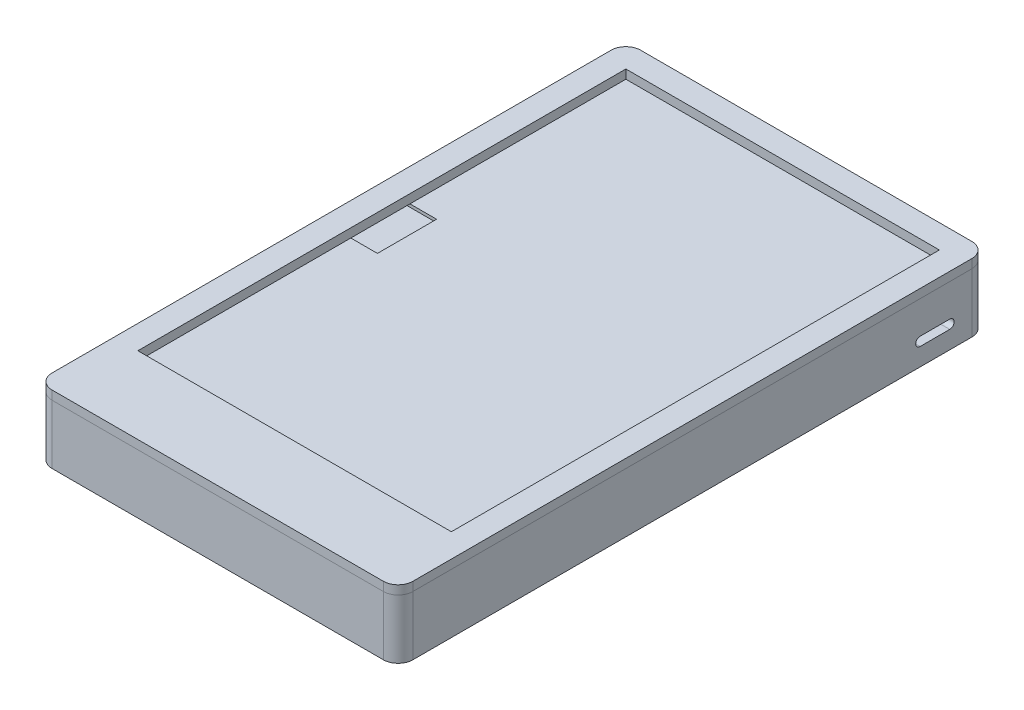
SolidWorks part; units mm, degrees
ref_plane "Front Plane" through (0, 0, 0) normal (0, 0, 1) x (1, 0, 0)
ref_plane "Top Plane" through (0, 0, 0) normal (0, 1, 0) x (1, 0, 0)
ref_plane "Right Plane" through (0, 0, 0) normal (1, 0, 0) x (0, 0, -1)
sketch "Sketch2" plane through (0, 0, 0) normal (0, 1, 0) x (1, 0, 0)
  line L1 (-56, -85.5) -> (56, -85.5)
  line L2 (-56, -85.5) -> (-56, 85.5)
  line L3 (-56, 85.5) -> (56, 85.5)
  line L4 (56, -85.5) -> (56, 85.5)
  line L5 (-56, -85.5) -> (56, 85.5) construction
  line L6 (-56, 85.5) -> (56, -85.5) construction
  point P0 (0, 0)
  dimension "D1" = 112
  dimension "D2" = 171
extrude "Boss-Extrude1" add sketch "Sketch2" along normal blind 2
sketch "Sketch3" plane through (0, 2, 0) normal (0, 1, 0) x (1, 0, 0)
  line L0 (61, -85.5) -> (61, 85.5)
  line L1 (56, 90.5) -> (-56, 90.5)
  line L2 (-61, 85.5) -> (-61, -85.5)
  line L4 (56, -85.5) -> (56, 85.5)
  line L5 (56, 85.5) -> (-56, 85.5)
  line L6 (-56, 85.5) -> (-56, -85.5)
  line L7 (-56, -85.5) -> (56, -85.5)
  line L8 (56, -85.5) -> (56, 85.5)
  line L9 (56, 85.5) -> (-56, 85.5)
  line L10 (-56, 85.5) -> (-56, -85.5)
  line L11 (-56, -85.5) -> (56, -85.5)
  line L12 (-61, 90.5) -> (-61, -90.5) construction
  line L13 (-61, -90.5) -> (61, -90.5) construction
  line L14 (61, -90.5) -> (61, 90.5) construction
  line L15 (61, 90.5) -> (-61, 90.5) construction
  line L16 (-61, -85.5) -> (-61, -103.5)
  line L17 (-56, -108.5) -> (56, -108.5)
  line L18 (61, -103.5) -> (61, -85.5)
  arc A2 (56, 90.5) -> (61, 85.5) centre (56, 85.5) cw
  arc A3 (-61, 85.5) -> (-56, 90.5) centre (-56, 85.5) cw
  arc A4 (61, -103.5) -> (56, -108.5) centre (56, -103.5) cw
  arc A5 (-61, -103.5) -> (-56, -108.5) centre (-56, -103.5) ccw
  point P23 (-61, -108.5)
  dimension "D3" = 23
  dimension "D4" = 5
  dimension "D5" = 5
  dimension "D1" = 0
  dimension "D2" = 5
extrude "Boss-Extrude2" add sketch "Sketch3" against normal blind 20 separate body
sketch "Sketch4" plane through (0, -18, 0) normal (0, -1, 0) x (1, 0, 0)
  line L0 (56, -90.5) -> (-56, -90.5) construction
  line L1 (61, 103.5) -> (61, -85.5) construction
  line L3 (-61, -85.5) -> (-61, 103.5) construction
  line L4 (56, -90.5) -> (-56, -90.5)
  line L5 (61, 103.5) -> (61, -85.5)
  line L7 (-61, -85.5) -> (-61, 103.5)
  line L8 (-56, 108.5) -> (56, 108.5) construction
  line L9 (-56, 108.5) -> (56, 108.5)
  arc A0 (-61, -85.5) -> (-56, -90.5) centre (-56, -85.5) ccw construction
  arc A1 (56, -90.5) -> (61, -85.5) centre (56, -85.5) ccw construction
  arc A4 (-61, -85.5) -> (-56, -90.5) centre (-56, -85.5) ccw
  arc A5 (56, -90.5) -> (61, -85.5) centre (56, -85.5) ccw
  arc A8 (-56, 108.5) -> (-61, 103.5) centre (-56, 103.5) ccw construction
  arc A9 (-56, 108.5) -> (-61, 103.5) centre (-56, 103.5) ccw
  arc A10 (61, 103.5) -> (56, 108.5) centre (56, 103.5) ccw construction
  arc A11 (61, 103.5) -> (56, 108.5) centre (56, 103.5) ccw
extrude "Boss-Extrude3" add sketch "Sketch4" along normal blind 3
sketch "Sketch6" plane through (0, -18, 0) normal (0, 1, 0) x (1, 0, 0)
  line L1 (-3.3, 60.5) -> (56, 60.5)
  line L2 (-3.3, 60.5) -> (-3.3, 85.5)
  line L3 (-3.3, 85.5) -> (56, 85.5)
  line L4 (56, 60.5) -> (56, 85.5)
  line L5 (-3.3, 60.5) -> (56, 85.5) construction
  line L6 (-3.3, 85.5) -> (56, 60.5) construction
  point P0 (26.35, 73)
  dimension "D1" = 25
  dimension "D2" = 59.3
extrude "Boss-Extrude4" add sketch "Sketch6" along normal blind 2 separate body
sketch "Sketch7" plane through (0, 0, 85.5) normal (0, 0, -1) x (-1, 0, 0)
  line L0 (-56, -18) -> (-56, 2) construction
  line L1 (-56, 0) -> (56, 0)
  line L2 (-56, 0) -> (-56, -18)
  line L3 (-56, -18) -> (56, -18)
  line L4 (56, 0) -> (56, -18)
  line L5 (56, 2) -> (-56, 2) construction
  dimension "D1" = 2
extrude "Cut-Extrude1" cut sketch "Sketch7" against normal offset from surface (21 mm away) 2 up to face at (0, -9.5, 108.5)
sketch "Sketch8" plane through (0, -18, 0) normal (0, 1, 0) x (1, 0, 0)
  line L0 (56, -106.5) -> (56, 85.5) construction
  line L1 (-4, 55.5) -> (56, 55.5)
  line L2 (-4, 55.5) -> (-4, -42.5)
  line L3 (-4, -42.5) -> (56, -42.5)
  line L4 (56, 55.5) -> (56, -42.5)
  line L5 (-3.3, 60.5) -> (56, 60.5) construction
  dimension "D1" = 5
  dimension "D2" = 60
  dimension "D3" = 98
extrude "Boss-Extrude5" add sketch "Sketch8" along normal blind 9 separate body
sketch "Sketch9" plane through (0, -18, 0) normal (0, 1, 0) x (1, 0, 0)
  line L0 (-56, 85.5) -> (-56, -106.5) construction
  line L1 (-56, 65.5) -> (-26, 65.5)
  line L2 (-56, 65.5) -> (-56, 0.5)
  line L3 (-56, 0.5) -> (-26, 0.5)
  line L4 (-26, 65.5) -> (-26, 0.5)
  line L5 (56, 85.5) -> (-56, 85.5) construction
  line L6 (-56, 85.5) -> (-56, -85.5) construction
  line L7 (-56, -4.5) -> (-25, -4.5)
  line L8 (-56, -4.5) -> (-56, -69.8)
  line L9 (-56, -69.8) -> (-25, -69.8)
  line L10 (-25, -4.5) -> (-25, -69.8)
  dimension "D1" = 30
  dimension "D2" = 65
  dimension "D3" = 20
  dimension "D4" = 31
  dimension "D5" = 65.3
  dimension "D6" = 5
extrude "Boss-Extrude6" add sketch "Sketch9" along normal blind 7 separate body
sketch "Sketch10" plane through (0, -18, 0) normal (0, 1, 0) x (1, 0, 0)
  line L0 (-10.5, -32.65) -> (-4.8608, -32.65)
  line L1 (-43, -6) -> (-43, -32.65)
  line L2 (-43, -74.3) -> (-10.5, -74.3)
  line L3 (-56, -6) -> (-46, -6)
  line L4 (-10.5, -74.3) -> (-10.5, -47.65)
  line L5 (-56, -1) -> (-24.5, -1)
  line L7 (-21.5, -1) -> (-7.8, -1)
  line L8 (-56, 85.5) -> (-56, -85.5) construction
  line L9 (-56, 85.5) -> (-56, -106.5) construction
  line L13 (-24.5, -1) -> (-24.5, 67)
  line L14 (-24.5, 67) -> (-56, 67)
  line L15 (-7.8608, -47) -> (-7.8608, 60) construction
  line L16 (-7.8, -1) -> (-7.8, 85.5)
  line L17 (-56, 0.5) -> (-26, 0.5) construction
  line L18 (-26, 0.5) -> (-26, 65.5) construction
  line L19 (-26, 65.5) -> (-56, 65.5) construction
  line L23 (-4.8608, -77.3) -> (-46, -77.3)
  line L24 (-21.5, -1) -> (-21.5, 70)
  line L25 (-21.5, 70) -> (-56, 70)
  line L26 (-56, -4) -> (-21.5, -4) construction
  line L27 (-21.5, -4) -> (-21.5, 70) construction
  line L28 (-4.8, 85.5) -> (-4.8, 59)
  line L29 (56, 85.5) -> (-56, 85.5) construction
  line L30 (-4.8, 59) -> (56, 59)
  line L31 (56, -106.5) -> (56, 85.5) construction
  line L32 (-3.3, 85.5) -> (-3.3, 60.5) construction
  line L33 (-3.3, 60.5) -> (56, 60.5) construction
  line L34 (56, -44) -> (15.1392, -44)
  line L35 (56, -85.5) -> (56, 85.5) construction
  line L36 (-4.8608, -32.65) -> (-4.8608, 57)
  line L37 (-7.8, 85.5) -> (-4.8, 85.5)
  line L39 (-4.8608, 57) -> (56, 57)
  line L40 (56, 55.5) -> (-4, 55.5) construction
  line L42 (56, -47) -> (15.1392, -47)
  line L43 (-4.8608, -77.3) -> (-4.8608, -47.65)
  line L46 (-7.8608, 60) -> (56, 60) construction
  line L47 (56, -47) -> (-7.8608, -47) construction
  line L48 (56, -44) -> (56, -47)
  line L49 (56, 59) -> (56, 57)
  line L51 (-56, 67) -> (-56, 70)
  line L52 (-56, -6) -> (-56, -1)
  line L54 (-46, -77.3) -> (-46, -47.65)
  line L55 (-43, -6) -> (-10.5, -6)
  line L56 (-46, -47.65) -> (-43, -47.65)
  line L57 (-46, -32.65) -> (-43, -32.65)
  line L58 (-43, -47.65) -> (-43, -74.3)
  line L59 (-46, -32.65) -> (-46, -6)
  line L60 (-10.5, -47.65) -> (-4.8608, -47.65)
  line L61 (-10.5, -32.65) -> (-10.5, -6)
  line L62 (-4.8608, -44) -> (-4.8608, 57) construction
  line L63 (15.1392, -44) -> (15.1392, -47)
  line L64 (56, -44) -> (-4.8608, -44) construction
  point P63 (0, 0)
  point P64 (0, 0)
  point P65 (0, 0)
  point P66 (0, 0)
  dimension "D2" = 3
  dimension "D3" = 5
  dimension "D4" = 1.5
  dimension "D5" = 1.5
  dimension "D6" = 1.5
  dimension "D7" = 3
  dimension "D9" = 1.5
  dimension "D10" = 1.5
  dimension "D11" = 3
  dimension "D12" = 15
  dimension "D13" = 1.5
  dimension "D16" = 101
  dimension "D17" = 20
  dimension "D18" = 10
  dimension "D19" = 32.5
  dimension "D20" = 68.3
  dimension "D14" = 60.8608
  dimension "D15" = 3
  dimension "D8" = 3
extrude "Boss-Extrude7" add sketch "Sketch10" along normal blind 3 separate body
combine bodies "Combine1" operation type add bodies to combine 109 105
combine bodies "Combine2" operation type add bodies to combine 111 155 156
sketch "Sketch11" plane through (-56, 0, 0) normal (1, 0, 0) x (0, 0, -1)
  line L0 (85.5, -18) -> (85.5, 2) construction
  line L1 (69.5, -5) -> (80.5, -5)
  line L2 (69.5, -5) -> (69.5, -11)
  line L3 (69.5, -11) -> (80.5, -11)
  line L4 (80.5, -5) -> (80.5, -11)
  point P8 (85.5, -8)
  point P9 (80.5, -8)
  dimension "D1" = 11
  dimension "D2" = 6
  dimension "D3" = 5
extrude "Cut-Extrude2" cut sketch "Sketch11" against normal blind 13
sketch "Sketch13" plane through (0, -18, 0) normal (0, 1, 0) x (1, 0, 0)
  line L0 (-56, -6) -> (-56, -106.5) construction
  line L1 (-56, -82.5) -> (56, -82.5)
  line L2 (-56, -82.5) -> (-56, -85.5)
  line L3 (-56, -85.5) -> (56, -85.5)
  line L4 (56, -82.5) -> (56, -85.5)
  dimension "D1" = 3
extrude "Boss-Extrude8" add sketch "Sketch13" along normal blind 13 separate body
combine bodies "Combine3" operation type add bodies to combine 114 113
sketch "Sketch15" plane through (0, -5, 0) normal (0, 1, 0) x (1, 0, 0)
  line L0 (-56, -82.5) -> (-56, -74.5)
  line L5 (-56, -74.5) -> (-53, -74.5)
  line L6 (-53, -74.5) -> (-53, -79.5)
  line L7 (-53, -79.5) -> (-48, -79.5)
  line L8 (-48, -79.5) -> (-48, -82.5)
  line L9 (56, -82.5) -> (-56, -82.5) construction
  line L10 (-48, -82.5) -> (-56, -82.5)
  dimension "D1" = 8
  dimension "D2" = 8
  dimension "D3" = 3
  dimension "D4" = 3
extrude "Boss-Extrude10" add sketch "Sketch15" against normal blind 3 separate body
mirror "Mirror2" about plane through (0, 0, 0) normal (1, 0, 0) of "Boss-Extrude10"
combine bodies "Combine7" operation type add bodies to combine 117 118
ref_plane "Plane1" through (0, 0, -1.5) normal (0, 0, 1) x (1, 0, 0)
sketch "Sketch16" plane through (0, -18, 0) normal (0, 1, 0) x (1, 0, 0)
  line L1 (-56, 85.5) -> (-48, 85.5)
  line L2 (-56, 85.5) -> (-56, 77.5)
  line L3 (-56, 77.5) -> (-53, 77.5)
  line L4 (-48, 85.5) -> (-48, 82.5)
  line L7 (-48, 82.5) -> (-53, 82.5)
  line L8 (-53, 77.5) -> (-53, 82.5)
  dimension "D1" = 3
  dimension "D2" = 3
  dimension "D3" = 5
  dimension "D4" = 5
extrude "Boss-Extrude11" add sketch "Sketch16" along normal blind 3 from offset 10 separate body
mirror "Mirror4" about plane through (0, 0, 0) normal (1, 0, 0) of "Boss-Extrude11"
sketch "Sketch17" plane through (0, 0, -85.5) normal (0, 0, 1) x (1, 0, 0)
  line L0 (-48, -5) -> (-48, -8) construction
  line L1 (-40, -6) -> (-29, -6)
  line L2 (-40, -6) -> (-40, -12)
  line L3 (-40, -12) -> (-29, -12)
  line L4 (-29, -6) -> (-29, -12)
  line L5 (-7.8, -18) -> (-56, -18) construction
  dimension "D1" = 11
  dimension "D2" = 6
  dimension "D3" = 8
  dimension "D4" = 6
extrude "Cut-Extrude3" cut sketch "Sketch17" against normal blind 13
sketch "Sketch18" plane through (0, -11, 0) normal (0, 1, 0) x (1, 0, 0)
  line L4 (-61, 80.5) -> (-61, 69.5)
  line L5 (-61, 69.5) -> (-56, 69.5)
  line L6 (-56, 69.5) -> (-56, 80.5)
  line L7 (-56, 80.5) -> (-61, 80.5)
  line L8 (-61, 80.5) -> (-61, 69.5)
  line L9 (-61, 69.5) -> (-56, 69.5)
  line L10 (-56, 69.5) -> (-56, 80.5)
  line L11 (-56, 80.5) -> (-61, 80.5)
  dimension "D1" = 0
extrude "Boss-Extrude12" add sketch "Sketch18" along normal up to surface (6 mm away) up to face at (-58.5, -5, -75)
sketch "Sketch19" plane through (0, -5, 0) normal (0, 1, 0) x (1, 0, 0)
  line L0 (-56, -74.5) -> (-56, -85.5) construction
  line L1 (-56, -82.5) -> (56, -82.5)
  line L2 (-56, -82.5) -> (-56, -85.5)
  line L3 (-56, -85.5) -> (56, -85.5)
  line L4 (56, -82.5) -> (56, -85.5)
  line L5 (56, -82.5) -> (-56, -82.5) construction
extrude "Boss-Extrude13" add sketch "Sketch19" along normal blind 2
sketch "Sketch20" plane through (0, -5, 0) normal (0, 1, 0) x (1, 0, 0)
  line L1 (-56, 85.5) -> (56, 85.5)
  line L2 (-56, 85.5) -> (-56, -82.5)
  line L3 (-56, -82.5) -> (56, -82.5)
  line L4 (56, 85.5) -> (56, -82.5)
extrude "Boss-Extrude14" add sketch "Sketch20" against normal blind 1 from surface at 2 separate body starting at face at (0, -3, 84)
sketch "Sketch21" plane through (0, -4, 0) normal (0, -1, 0) x (-1, 0, 0)
  line L1 (56, -8.5) -> (46, -8.5)
  line L2 (56, -8.5) -> (56, 11.5)
  line L3 (56, 11.5) -> (46, 11.5)
  line L4 (46, -8.5) -> (46, 11.5)
  line L5 (56, -8.5) -> (46, 11.5) construction
  line L6 (56, 11.5) -> (46, -8.5) construction
  line L8 (56, 85.5) -> (56, -82.5) construction
  point P5 (56, 1.5)
  point P6 (56, 1.5)
  point P7 (0, 0)
  dimension "D1" = 20
  dimension "D2" = 10
extrude "Cut-Extrude4" cut sketch "Sketch21" against normal blind 1
sketch "Sketch22" plane through (0, 2, 0) normal (0, 1, 0) x (1, 0, 0)
  line L0 (56, -85.5) -> (56, 85.5) construction
  line L1 (56, 85.5) -> (-56, 85.5) construction
  line L2 (-56, 85.5) -> (-56, -85.5) construction
  line L3 (-56, -85.5) -> (56, -85.5) construction
  line L4 (56, -85.5) -> (56, 85.5)
  line L5 (56, 85.5) -> (-56, 85.5)
  line L6 (-56, 85.5) -> (-56, -85.5)
  line L7 (-56, -85.5) -> (56, -85.5)
  line L8 (-53, 82.5) -> (-53, -82.5)
  line L9 (-53, -82.5) -> (53, -82.5)
  line L10 (53, -82.5) -> (53, 82.5)
  line L11 (53, 82.5) -> (-53, 82.5)
  dimension "D1" = 3
extrude "Boss-Extrude15" add sketch "Sketch22" against normal blind 3
ref_plane "Plane2" through (0, -1, 0) normal (0, -1, 0) x (-1, 0, 0)
split "Split1" trim tools "Plane2" bodies to split 127 resulting bodies 128 129
sketch "Sketch23" plane through (0, -18, 0) normal (0, 1, 0) x (1, 0, 0)
  line L0 (56, -106.5) -> (56, 85.5) construction
  line L1 (-56, -85.5) -> (56, -85.5)
  line L2 (-56, -85.5) -> (-56, -88.5)
  line L3 (-56, -88.5) -> (56, -88.5)
  line L4 (56, -85.5) -> (56, -88.5)
  dimension "D1" = 3
extrude "Boss-Extrude16" add sketch "Sketch23" along normal up to surface (17 mm away)
delete or keep bodies "Body-Delete/Keep 1" type delete bodies bodies 101
sketch "Sketch24" plane through (0, -4, 0) normal (0, -1, 0) x (-1, 0, 0)
  line L1 (56, 85.5) -> (-56, 85.5)
  line L2 (56, 85.5) -> (56, -85.5)
  line L3 (56, -85.5) -> (-56, -85.5)
  line L4 (-56, 85.5) -> (-56, -85.5)
extrude "Boss-Extrude17" add sketch "Sketch24" along normal blind 2 separate body
sketch "Sketch25" plane through (0, 0, 88.5) normal (0, 0, 1) x (1, 0, 0)
  line L0 (-56, -18) -> (56, -18) construction
  line L1 (-46, -18) -> (46, -18)
  line L2 (-46, -18) -> (-46, -10)
  line L3 (-46, -10) -> (46, -10)
  line L4 (46, -18) -> (46, -10)
  line L5 (-56, -1) -> (-56, -18) construction
  line L6 (56, -1) -> (56, -18) construction
  dimension "D1" = 10
  dimension "D2" = 10
  dimension "D3" = 8
extrude "Cut-Extrude5" cut sketch "Sketch25" against normal blind 6
sketch "Sketch26" plane through (0, 0, 0) normal (0, -1, 0) x (-1, 0, 0)
  line L0 (0, -85.5) -> (0, -108.5) construction
  line L1 (15.5, -89) -> (-15.5, -89)
  line L2 (15.5, -89) -> (15.5, -106)
  line L3 (15.5, -106) -> (-15.5, -106)
  line L4 (-15.5, -89) -> (-15.5, -106)
  line L5 (15.5, -89) -> (-15.5, -106) construction
  line L6 (15.5, -106) -> (-15.5, -89) construction
  line L7 (56, -85.5) -> (-56, -85.5) construction
  line L8 (56, -108.5) -> (-56, -108.5) construction
  line L9 (56, -106.5) -> (-56, -106.5) construction
  line L10 (-50.1, -89) -> (-50.1, -106)
  line L11 (-19.1, -106) -> (-50.1, -106)
  line L12 (-19.1, -89) -> (-19.1, -106)
  line L13 (-19.1, -89) -> (-50.1, -89)
  line L14 (19.9, -89) -> (19.9, -106)
  line L15 (50.9, -106) -> (19.9, -106)
  line L16 (50.9, -89) -> (50.9, -106)
  line L17 (50.9, -89) -> (19.9, -89)
  line L18 (56, -106.5) -> (56, -85.5) construction
  line L20 (-56, -106.5) -> (-56, -85.5) construction
  line L21 (56, -85.5) -> (-56, -85.5) construction
  line L22 (-56, -106.5) -> (-56, -85.5)
  line L23 (56, -106.5) -> (-56, -106.5)
  line L24 (56, -106.5) -> (56, -85.5)
  line L25 (56, -85.5) -> (-56, -85.5)
  point P0 (0, -97.5)
  dimension "D1" = 17
  dimension "D2" = 31
  dimension "D3" = 0.5
  dimension "D6" = 5.1
  dimension "D7" = 75.1
  dimension "D4" = 2
  dimension "D5" = 2
extrude "Boss-Extrude18" add sketch "Sketch26" along normal blind 1
sketch "Sketch27" plane through (0, -15, 0) normal (0, 1, 0) x (1, 0, 0)
  line L0 (-21.5, 70) -> (-56, 70) construction
  line L1 (-48, 70) -> (-28.5, 70)
  line L2 (-48, 70) -> (-48, 67)
  line L3 (-48, 67) -> (-28.5, 67)
  line L4 (-28.5, 70) -> (-28.5, 67)
  line L5 (-56, 67) -> (-24.5, 67) construction
  line L6 (-56, 85.5) -> (-56, -85.5) construction
  dimension "D1" = 8
  dimension "D2" = 4
extrude "Cut-Extrude6" cut sketch "Sketch27" against normal up to surface (3 mm away) up to face at (25.6, -18, -72.25)
sketch "Sketch28" plane through (-56, 0, 0) normal (1, 0, 0) x (0, 0, -1)
  line L0 (67, -18) -> (-1, -18) construction
  line L1 (-82.5, -8) -> (-82.5, -18) construction
  line L2 (-6, -18) -> (-82.5, -18) construction
  ellipse E0 centre (10.9166, -15.2) end of major axis (5.6054, -15.2) minor radius 2.7092
  dimension "D1" = 2.8
  dimension "D2" = 88.1054
  dimension "D3" = 93.4166
  dimension "D4" = 0.0908
extrude "Cut-Extrude7" cut sketch "Sketch28" against normal blind 10
sketch "Sketch29" plane through (-56, 0, 0) normal (1, 0, 0) x (0, 0, -1)
  line L0 (10.9166, -15.2) -> (85.5, -15.2) construction
  line L1 (85.5, -18) -> (85.5, -8) construction
  line L2 (46.1027, -18) -> (58.3512, -18)
  line L3 (67, -18) -> (-1, -18) construction
  line L4 (-82.5, -8) -> (-82.5, -18) construction
  line L5 (-6, -18) -> (-82.5, -18) construction
  ellipse E0 centre (10.9166, -15.2) end of major axis (5.6054, -15.2) minor radius 2.7092 construction
  ellipse E1 centre (23.4365, -15.2) end of major axis (18.1254, -15.2) minor radius 2.7092
  ellipse E2 centre (52.702, -15.2) end of major axis (44.4022, -15.6719) minor radius 4.1446 (58.3512, -18) -> (46.1027, -18) ccw
  dimension "D1" = 100.6254
  dimension "D2" = 105.9365
  dimension "D3" = 126.9022
  dimension "D4" = 128.6027
  dimension "D5" = 134.9668
  dimension "D6" = 135.202
  dimension "D7" = 0.0908
extrude "Cut-Extrude8" cut sketch "Sketch29" against normal blind 2
sketch "Sketch30" plane through (-58, 0, 0) normal (1, 0, 0) x (0, 0, -1)
  ellipse E1 centre (23.4365, -15.2) end of major axis (18.1254, -15.2) minor radius 2.7092
  ellipse E2 centre (23.4365, -15.2) end of major axis (18.1254, -15.2) minor radius 2.7092
  dimension "D1" = 0
extrude "Cut-Extrude9" cut sketch "Sketch30" against normal blind 11.5
sketch "Sketch31" plane through (-61, 0, 0) normal (-1, 0, 0) x (0, 0, 1)
  ellipse E0 centre (-10.9166, -15.2) end of major axis (-5.6054, -15.2) minor radius 2.7092 construction
  ellipse E1 centre (-10.9166, -15.2) end of major axis (-5.6054, -15.2) minor radius 2.7092
extrude "Boss-Extrude19" add sketch "Sketch31" against normal blind 3
sketch "Sketch32" plane through (0, 0, -85.5) normal (0, 0, 1) x (1, 0, 0)
  line L1 (-3.3, -11) -> (56, -11)
  line L6 (-3.3, -18) -> (-3.3, -11)
  line L7 (-3.3, -18) -> (56, -18)
  line L8 (56, -18) -> (56, -8) construction
  line L9 (56, -18) -> (56, -11)
  dimension "D1" = 7
extrude "Cut-Extrude10" cut sketch "Sketch32" against normal blind 3.5
sketch "Sketch33" plane through (0, 0, -89) normal (0, 0, 1) x (1, 0, 0)
  line L2 (-4.8, -16) -> (8.2, -16)
  line L3 (-4.8, -16) -> (-4.8, -12)
  line L4 (-4.8, -12) -> (8.2, -12)
  line L5 (8.2, -16) -> (8.2, -12)
  line L6 (-4.8, -16) -> (8.2, -12) construction
  line L7 (-4.8, -12) -> (8.2, -16) construction
  line L8 (-3.3, -11) -> (-3.3, -18) construction
  line L9 (-3.3, -18) -> (56, -18) construction
  dimension "D1" = 13
  dimension "D2" = 4
  dimension "D3" = 1.5
  dimension "D4" = 2
extrude "Cut-Extrude11" cut sketch "Sketch33" against normal blind 3
sketch "Sketch35" plane through (56, 0, 0) normal (-1, 0, 0) x (0, 0, 1)
  line L0 (-78, -13.5) -> (-68, -13.5) construction
  line L1 (-78, -12) -> (-68, -12)
  line L2 (-78, -15) -> (-68, -15)
  line L3 (-60.5, -16) -> (-85.5, -16) construction
  line L4 (-73, -16) -> (-73, -12) construction
  arc A0 (-78, -12) -> (-78, -15) centre (-78, -13.5) ccw
  arc A1 (-68, -15) -> (-68, -12) centre (-68, -13.5) ccw
  point P2 (-73, -13.5)
  dimension "D1" = 10
  dimension "D2" = 3
  dimension "D3" = 1
extrude "Cut-Extrude13" cut sketch "Sketch35" against normal blind 22
chamfer "Chamfer1" distance 3 angle 45 8 edges at (56, -8, 78.5) (52, -8, 82.5) (-56, -8, 78.5) (-52, -8, 82.5) (-52, -8, -85.5) (-56, -8, -81.5) (56, -8, -81.5) (52, -8, -85.5)
sketch "Sketch37" plane through (0, 0, -89) normal (0, 0, -1) x (-1, 0, 0)
  line L4 (3.3, -12) -> (3.3, -16)
  line L5 (3.3, -16) -> (4.8, -16)
  line L6 (4.8, -16) -> (4.8, -12)
  line L7 (4.8, -12) -> (3.3, -12)
  line L8 (3.3, -12) -> (3.3, -16)
  line L9 (3.3, -16) -> (4.8, -16)
  line L10 (4.8, -16) -> (4.8, -12)
  line L11 (4.8, -12) -> (3.3, -12)
  dimension "D1" = 0
extrude "Cut-Extrude14" cut sketch "Sketch37" against normal blind 10
sketch "Sketch38" plane through (0, 0, -85.5) normal (0, 0, 1) x (1, 0, 0)
  line L4 (-3.3, -18) -> (-3.3, -16)
  line L5 (-3.3, -16) -> (-4.8, -16)
  line L6 (-4.8, -16) -> (-4.8, -18)
  line L7 (-4.8, -18) -> (-3.3, -18)
  line L8 (-3.3, -18) -> (-3.3, -16)
  line L9 (-3.3, -16) -> (-4.8, -16)
  line L10 (-4.8, -16) -> (-4.8, -18)
  line L11 (-4.8, -18) -> (-3.3, -18)
  dimension "D1" = 0
extrude "Cut-Extrude15" cut sketch "Sketch38" against normal up to surface (3.5 mm away) up to face at (14.4, -14.25, -89)
sketch "Sketch39" plane through (-3.3, 0, 0) normal (1, 0, 0) x (0, 0, -1)
  line L4 (85.5, -11) -> (85.5, -12)
  line L5 (85.5, -12) -> (89, -12)
  line L6 (89, -12) -> (89, -11)
  line L7 (89, -11) -> (85.5, -11)
  line L8 (85.5, -11) -> (85.5, -12)
  line L9 (85.5, -12) -> (89, -12)
  line L10 (89, -12) -> (89, -11)
  line L11 (89, -11) -> (85.5, -11)
  dimension "D1" = 0
extrude "Cut-Extrude16" cut sketch "Sketch39" against normal up to surface (1.5 mm away) up to face at (-4.8, -15.25, -81)
sketch "Sketch40" plane through (0, -5, 0) normal (0, 1, 0) x (1, 0, 0)
  line L0 (56, 77.5) -> (56, 85.5) construction
  line L1 (56, 85.5) -> (48, 85.5) construction
  line L2 (48, 85.5) -> (48, 82.5) construction
  line L3 (48, 82.5) -> (53, 82.5) construction
  line L4 (53, 82.5) -> (53, 77.5) construction
  line L5 (53, 77.5) -> (56, 77.5) construction
  line L6 (-56, -82.5) -> (-48, -82.5)
  line L7 (-48, -82.5) -> (-48, -79.5)
  line L8 (-48, -79.5) -> (-53, -79.5)
  line L9 (-53, -79.5) -> (-53, -74.5)
  line L10 (-53, -74.5) -> (-56, -74.5)
  line L11 (-56, -74.5) -> (-56, -82.5)
  line L12 (-56, -82.5) -> (-48, -82.5)
  line L13 (-48, -82.5) -> (-48, -79.5)
  line L14 (-48, -79.5) -> (-53, -79.5)
  line L15 (-53, -79.5) -> (-53, -74.5)
  line L16 (-53, -74.5) -> (-56, -74.5)
  line L18 (48, -82.5) -> (56, -82.5)
  line L19 (56, -82.5) -> (56, -74.5)
  line L20 (56, -74.5) -> (53, -74.5)
  line L21 (53, -74.5) -> (53, -79.5)
  line L22 (53, -79.5) -> (48, -79.5)
  line L23 (48, -79.5) -> (48, -82.5)
  line L24 (48, -82.5) -> (56, -82.5)
  line L26 (56, -74.5) -> (53, -74.5)
  line L27 (53, -74.5) -> (53, -79.5)
  line L28 (53, -79.5) -> (48, -79.5)
  line L29 (48, -79.5) -> (48, -82.5)
  line L30 (-56, 85.5) -> (-56, 77.5) construction
  line L31 (-56, 77.5) -> (-53, 77.5) construction
  line L32 (-53, 77.5) -> (-53, 82.5) construction
  line L33 (-53, 82.5) -> (-48, 82.5) construction
  line L34 (-48, 82.5) -> (-48, 85.5) construction
  line L35 (-48, 85.5) -> (-56, 85.5) construction
  line L36 (56, 77.5) -> (56, 85.5)
  line L37 (56, 85.5) -> (48, 85.5)
  line L38 (48, 85.5) -> (48, 82.5)
  line L39 (48, 82.5) -> (53, 82.5)
  line L40 (53, 82.5) -> (53, 77.5)
  line L41 (53, 77.5) -> (56, 77.5)
  line L42 (-56, 85.5) -> (-56, 77.5)
  line L43 (-56, 77.5) -> (-53, 77.5)
  line L44 (-53, 77.5) -> (-53, 82.5)
  line L45 (-53, 82.5) -> (-48, 82.5)
  line L46 (-48, 82.5) -> (-48, 85.5)
  line L47 (-48, 85.5) -> (-56, 85.5)
  line L54 (-56, -74.5) -> (-56, -82.5)
  line L55 (56, -82.5) -> (56, -74.5)
  dimension "D1" = 0
  dimension "D2" = 0
extrude "Boss-Extrude20" add sketch "Sketch40" along normal blind 1
sketch "Sketch41" plane through (0, -1, 0) normal (0, 1, 0) x (1, 0, 0)
  line L0 (-61, -102.5) -> (-56, -102.5) construction
  line L1 (-61, -103.5) -> (-61, 85.5) construction
  line L2 (-56, -88.5) -> (-56, -106.5) construction
  line L3 (-56, -108.5) -> (56, -108.5) construction
  line L4 (-61, 84.5) -> (-56, 84.5) construction
  line L5 (-56, 11.5) -> (-56, 85.5) construction
  line L6 (56, 90.5) -> (-56, 90.5) construction
  line L7 (-56, 0) -> (-61, 0) construction
  line L8 (-56, 85.5) -> (-56, -85.5) construction
  circle A0 centre (-58.5, -102.5) radius 2
  circle A1 centre (-58.5, 84.5) radius 2
  circle A2 centre (-58.5, 0) radius 2
  point P25 (0, 0)
  dimension "D1" = 4
  dimension "D3" = 4
  dimension "D4" = 6
  dimension "D5" = 4
  dimension "D2" = 6
extrude "Boss-Extrude21" add sketch "Sketch41" along normal blind 2
hole_wizard "Ø1.0mm Dowel Hole1" positions "Sketch55" profile "Sketch57" hole size "Ø1.0" standard "ANSI Metric"
sketch "Sketch55" plane through (0, 1, 0) normal (0, 1, 0) x (1, 0, 0)
  point P0 (-58.5, -102.5)
  point P3 (-58.5, 0)
  point P6 (-58.5, 84.5)
sketch "Sketch57" plane through (-58.5, 1, 102.5) normal (1, 0, 0) x (0, 0, 1)
  line L0 (0, 0) -> (0, 3.3004)
  line L1 (0, 3.3004) -> (0.5, 3)
  line L2 (0.5, 3) -> (0.5, 0)
  line L5 (0.5, 0) -> (0, 0)
  line L10 (0, 3.3004) -> (-0.5, 3) construction
  line L11 (0, -6.35) -> (0, 107.95) construction
  dimension "Hole Dia." = 1
  dimension "Hole Depth" = 3
  dimension "Drill Angle" = 118
mirror "Mirror5" about plane through (0, 0, 0) normal (1, 0, 0) of "Boss-Extrude21", "Ø1.0mm Dowel Hole1"
sketch "Sketch59" plane through (0, 1, 0) normal (0, 1, 0) x (1, 0, 0)
  circle A0 centre (58.5, 0) radius 2 construction
  circle A1 centre (58.5, 84.5) radius 2 construction
  circle A2 centre (-58.5, 84.5) radius 2 construction
  circle A3 centre (-58.5, 0) radius 2 construction
  circle A4 centre (-58.5, -102.5) radius 2 construction
  circle A5 centre (58.5, -102.5) radius 2 construction
  circle A6 centre (58.5, 0) radius 2
  circle A7 centre (58.5, 84.5) radius 2
  circle A8 centre (-58.5, 84.5) radius 2
  circle A9 centre (-58.5, 0) radius 2
  circle A10 centre (-58.5, -102.5) radius 2
  circle A11 centre (58.5, -102.5) radius 2
extrude "Cut-Extrude17" cut sketch "Sketch59" against normal blind 2
other "Save Bodies1"
